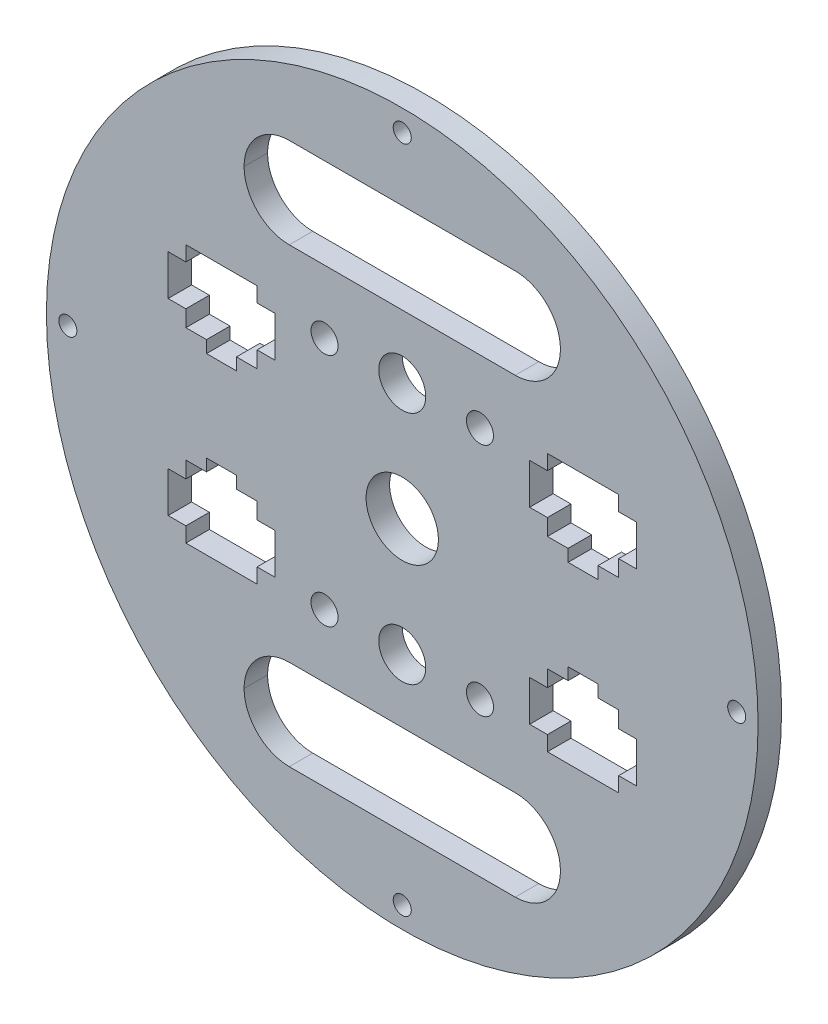
SolidWorks part; units mm, degrees
ref_plane "前视基准面" through (0, 0, 0) normal (0, 0, 1) x (1, 0, 0)
ref_plane "上视基准面" through (0, 0, 0) normal (0, 1, 0) x (1, 0, 0)
ref_plane "右视基准面" through (0, 0, 0) normal (1, 0, 0) x (0, 0, -1)
sketch "草图1" plane through (0, 0, 0) normal (0, 0, 1) x (1, 0, 0)
  circle A0 centre (0, 0) radius 50
  dimension "D1" = 100
extrude "凸台-拉伸1" add sketch "草图1" along normal blind 3.302
sketch "草图4" plane through (0, 0, 3.302) normal (0, 0, 1) x (1, 0, 0)
  circle A0 centre (0, 0) radius 5.08
  dimension "D1" = 10.16
extrude "切除-拉伸3" cut sketch "草图4" against normal through all
sketch "草图7" plane through (0, 0, 3.302) normal (0, 0, 1) x (1, 0, 0)
  circle A0 centre (0, 46.99) radius 1.27
  circle A1 centre (46.99, 0) radius 1.27
  circle A2 centre (0, -46.99) radius 1.27
  circle A3 centre (-46.99, 0) radius 1.27
  point P12 (0, 0)
  dimension "D1" = 2.54
  dimension "D2" = 46.99
  dimension "D3" = 4
extrude "切除-拉伸6" cut sketch "草图7" against normal through all
sketch "Sketch3" plane through (0, 0, 3.302) normal (0, 0, 1) x (1, 0, 0)
  circle A0 centre (0, 16.51) radius 3.302
  circle A1 centre (10.922, 16.51) radius 1.9
  circle A2 centre (-10.922, 16.51) radius 1.9
  dimension "D1" = 16.51
  dimension "D2" = 10.922
  dimension "D3" = 10.922
  dimension "D4" = 3.8
  dimension "D5" = 3.8
  dimension "D6" = 6.604
extrude "Cut-Extrude1" cut sketch "Sketch3" against normal through all
mirror "Mirror3" about plane through (0, 0, 0) normal (0, 1, 0) of "Cut-Extrude1"
sketch "Sketch10" plane through (0, 0, 3.302) normal (0, 0, 1) x (1, 0, 0)
  line L0 (-25.4, -8.0516) -> (-25.4, -18.1532) construction
  line L5 (-20.4, -18.1532) -> (-30.4, -18.1532)
  line L6 (-30.4, -18.1532) -> (-30.4, -16.0548)
  line L7 (-30.4, -16.0548) -> (-32.9, -16.0548)
  line L8 (-32.9, -16.0548) -> (-32.9, -10.3532)
  line L9 (-32.9, -10.3532) -> (-30.4, -10.3532)
  line L10 (-30.4, -10.3532) -> (-30.4, -8.0516)
  line L11 (-30.4, -8.0516) -> (-27.5016, -8.0516)
  line L12 (-27.5016, -8.0516) -> (-27.5016, -6.35)
  line L13 (-27.5016, -6.35) -> (-23.2984, -6.35)
  line L14 (-20.4, -18.1532) -> (-20.4, -16.0548)
  line L15 (-20.4, -16.0548) -> (-17.9, -16.0548)
  line L16 (-17.9, -16.0548) -> (-17.9, -10.3532)
  line L17 (-17.9, -10.3532) -> (-20.4, -10.3532)
  line L18 (-20.4, -10.3532) -> (-20.4, -8.0516)
  line L19 (-23.2984, -8.0516) -> (-23.2984, -6.35)
  line L20 (-20.4, -8.0516) -> (-23.2984, -8.0516)
  point P26 (-25.4, -6.35)
  dimension "D1" = 11.8032
  dimension "D2" = 10.1016
  dimension "D3" = 5.7016
  dimension "D4" = 2.3016
  dimension "D5" = 15
  dimension "D6" = 4.2032
  dimension "D7" = 10
  dimension "D8" = 6.35
  dimension "D9" = 25.4
extrude "Cut-Extrude4" cut sketch "Sketch10" against normal through all
mirror "Mirror4" about plane through (0, 0, 0) normal (0, 1, 0) of "Cut-Extrude4"
mirror "Mirror5" about plane through (0, 0, 0) normal (1, 0, 0) of "Mirror4"
sketch "Sketch11" plane through (0, 0, 3.302) normal (0, 0, 1) x (1, 0, 0)
  line L1 (-22.225, 38.1) -> (22.225, 38.1)
  line L2 (-22.225, 38.1) -> (-22.225, 25.4)
  line L3 (-22.225, 25.4) -> (22.225, 25.4)
  line L4 (22.225, 38.1) -> (22.225, 25.4)
  line L5 (-22.225, 38.1) -> (22.225, 25.4) construction
  line L6 (-22.225, 25.4) -> (22.225, 38.1) construction
  point P0 (0, 31.75)
  dimension "D1" = 31.75
  dimension "D2" = 44.45
  dimension "D3" = 12.7
extrude "Cut-Extrude5" cut sketch "Sketch11" against normal through all
fillet "Fillet1" radius 6.35 4 edges at (22.225, 25.4, 1.651) (22.225, 38.1, 1.651) (-22.225, 38.1, 1.651) (-22.225, 25.4, 1.651)
mirror "Mirror6" about plane through (0, 0, 0) normal (0, 1, 0) of "Fillet1", "Cut-Extrude5"
